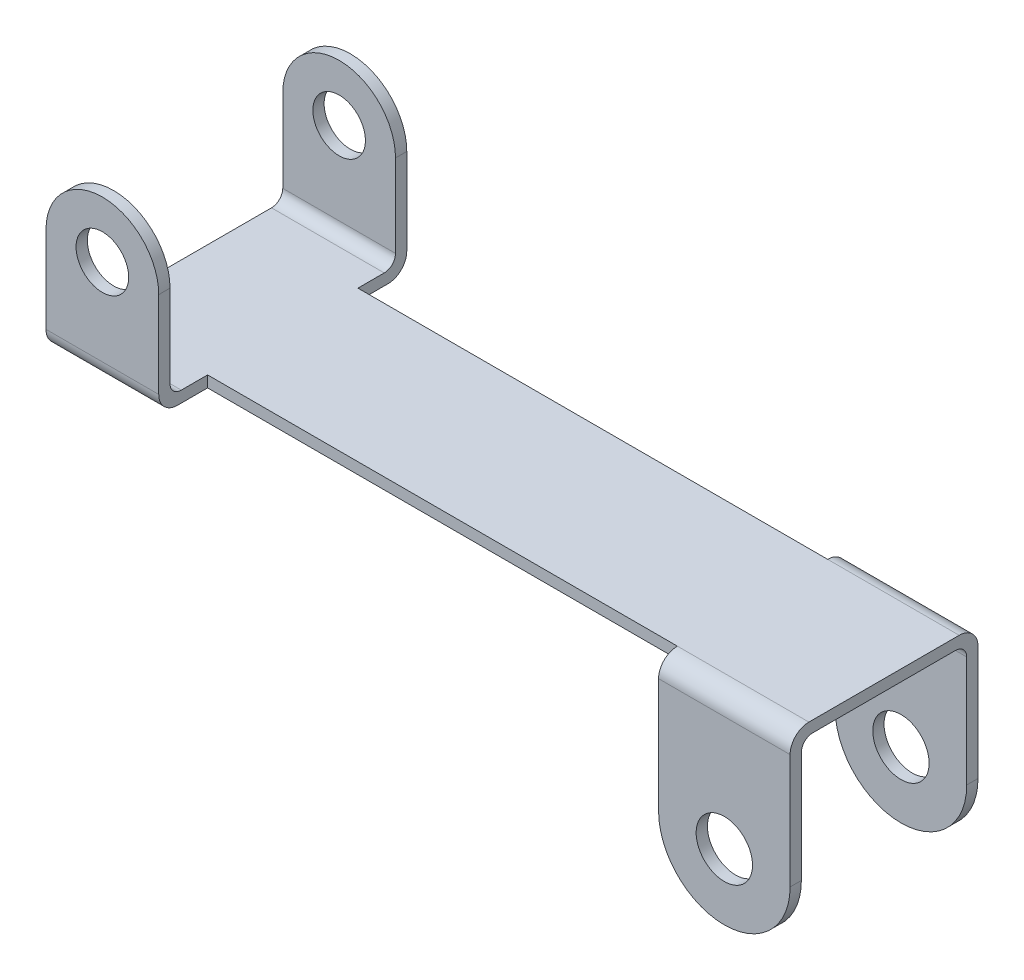
SolidWorks part; units mm, degrees
ref_plane "Front Plane" through (0, 0, 0) normal (0, 0, 1) x (1, 0, 0)
ref_plane "Top Plane" through (0, 0, 0) normal (0, 1, 0) x (1, 0, 0)
ref_plane "Right Plane" through (0, 0, 0) normal (1, 0, 0) x (0, 0, -1)
sketch "Sketch1" plane through (0, 0, 0) normal (0, 1, 0) x (1, 0, 0)
  line L1 (0, 0) -> (19, 0)
  line L2 (0, 0) -> (0, -4)
  line L3 (0, -4) -> (19, -4)
  line L4 (19, 0) -> (19, -4)
  dimension "D1" = 4
  dimension "D2" = 19
extrude "Boss-Extrude1" add sketch "Sketch1" along normal blind 0.3
sketch "Sketch2" plane through (0, 0, 0) normal (0, -1, 0) x (1, 0, 0)
  line L1 (0, 0) -> (3, 0)
  line L2 (0, 0) -> (0, -1.3)
  line L3 (0, -1.3) -> (3, -1.3)
  line L4 (3, 0) -> (3, -1.3)
  line L5 (0, 4) -> (3, 4)
  line L6 (0, 4) -> (0, 5.3)
  line L7 (0, 5.3) -> (3, 5.3)
  line L8 (3, 4) -> (3, 5.3)
  dimension "D1" = 3
  dimension "D2" = 1.3
extrude "Boss-Extrude2" add sketch "Sketch2" against normal up to surface (0.3 mm away) up to face at (9.5, 0.3, 2)
sketch "Sketch3" plane through (0, 0.3, 0) normal (0, 1, 0) x (1, 0, 0)
  line L1 (0, 1.3) -> (3, 1.3)
  line L2 (0, 1.3) -> (0, 1)
  line L3 (0, 1) -> (3, 1)
  line L4 (3, 1.3) -> (3, 1)
  line L5 (0, 1.3) -> (0, -5.3) construction
  line L6 (3, -5.3) -> (0, -5.3)
  line L7 (3, -5.3) -> (3, -5)
  line L8 (3, -5) -> (0, -5)
  line L9 (0, -5.3) -> (0, -5)
  dimension "D1" = 0.3
extrude "Boss-Extrude3" add sketch "Sketch3" along normal blind 4
fillet "Fillet1" 2 edges at (3, 4.3, -1.15) (0, 4.3, -1.15) type full round first side face at (3, 1.5333, -0.7667) second side face at (0, 2.225, 2) middle face at (1.5, 4.3, -1.15)
fillet "Fillet2" 2 edges at (3, 4.3, 5.15) (0, 4.3, 5.15) type full round first side face at (3, 1.5333, 4.7667) second side face at (0, 1.85, 2) middle face at (1.5, 4.3, 5.15)
sketch "Sketch4" plane through (0, 0, -1.3) normal (0, 0, -1) x (-1, 0, 0)
  line L0 (-3, 2.8) -> (0, 2.8) construction
  circle A0 centre (-1.5, 2.8) radius 0.7
  dimension "D1" = 1.4
extrude "Cut-Extrude1" cut sketch "Sketch4" against normal through all
sketch "Sketch6" plane through (0, 0.3, 0) normal (0, 1, 0) x (1, 0, 0)
  line L1 (19, 0) -> (15.5, 0)
  line L2 (19, 0) -> (19, 0.5)
  line L3 (19, 0.5) -> (15.5, 0.5)
  line L4 (15.5, 0) -> (15.5, 0.5)
  line L5 (19, -4) -> (15.5, -4)
  line L6 (19, -4) -> (19, -4.5)
  line L7 (19, -4.5) -> (15.5, -4.5)
  line L8 (15.5, -4) -> (15.5, -4.5)
  dimension "D1" = 0.5
  dimension "D2" = 3.5
extrude "Boss-Extrude4" add sketch "Sketch6" against normal up to surface (0.3 mm away) up to face at (6.25, 0, 2)
sketch "Sketch7" plane through (0, 0, 0) normal (0, -1, 0) x (1, 0, 0)
  line L0 (19, 4.5) -> (19, -0.5) construction
  line L1 (15.5, -0.5) -> (19, -0.5)
  line L2 (15.5, -0.5) -> (15.5, -0.2)
  line L3 (15.5, -0.2) -> (19, -0.2)
  line L4 (19, -0.5) -> (19, -0.2)
  line L6 (15.5, 4.5) -> (19, 4.5)
  line L7 (15.5, 4.5) -> (15.5, 4.2)
  line L8 (15.5, 4.2) -> (19, 4.2)
  line L9 (19, 4.5) -> (19, 4.2)
  dimension "D1" = 0.3
  dimension "D2" = 0.3
extrude "Boss-Extrude5" add sketch "Sketch7" along normal blind 5
fillet "Fillet3" 2 edges at (15.5, -5, 4.35) (19, -5, 4.35) type full round first side face at (15.5, -1.5667, 4.2333) second side face at (19, -2.425, 2) middle face at (17.25, -5, 4.35)
fillet "Fillet4" 2 edges at (15.5, -5, -0.35) (19, -5, -0.35) type full round first side face at (15.5, -1.5667, -0.2333) second side face at (19, -1.9875, 2) middle face at (17.25, -5, -0.35)
sketch "Sketch8" plane through (0, 0, 4.5) normal (0, 0, 1) x (1, 0, 0)
  circle A0 centre (17.25, -3.25) radius 0.75
  dimension "D1" = 1.5
extrude "Cut-Extrude2" cut sketch "Sketch8" against normal through all
fillet "Fillet5" radius 0.3 4 edges at (17.25, 0, 4.2) (17.25, 0, -0.2) (1.5, 0.3, -1) (1.5, 0.3, 5)
fillet "Fillet6" radius 0.5 4 edges at (1.5, 0, 5.3) (1.5, 0, -1.3) (17.25, 0.3, 4.5) (17.25, 0.3, -0.5)
